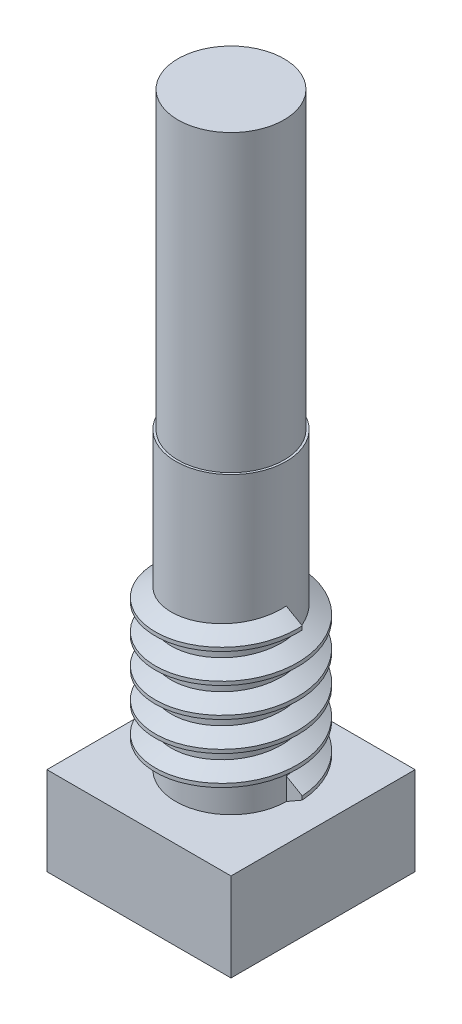
SolidWorks part; units mm, degrees
ref_plane "Front Plane" through (0, 0, 0) normal (0, 0, 1) x (1, 0, 0)
ref_plane "Top Plane" through (0, 0, 0) normal (0, 1, 0) x (1, 0, 0)
ref_plane "Right Plane" through (0, 0, 0) normal (1, 0, 0) x (0, 0, -1)
sketch "Sketch2" plane through (0, 0, 0) normal (0, 1, 0) x (1, 0, 0)
  line L1 (3.9688, -3.9688) -> (-3.9687, -3.9688)
  line L2 (3.9688, -3.9688) -> (3.9688, 3.9687)
  line L3 (3.9688, 3.9687) -> (-3.9687, 3.9687)
  line L4 (-3.9687, -3.9688) -> (-3.9687, 3.9687)
  line L5 (3.9688, -3.9688) -> (-3.9687, 3.9687) construction
  line L6 (3.9688, 3.9687) -> (-3.9687, -3.9688) construction
  dimension "D2" = 7.9375
  dimension "D3" = 7.9375
extrude "Boss-Extrude1" add sketch "Sketch2" along normal blind 3.81
sketch "Sketch3" plane through (0, 3.81, 0) normal (0, 1, 0) x (1, 0, 0)
  circle A0 centre (0, 0) radius 2.3825
  dimension "D1" = 4.765
extrude "Boss-Extrude2" add sketch "Sketch3" along normal blind 25.4
thread "Thread2" pitch 1.27 method extrude profile "Thread Profile2" start angle 0, offset 0, length 6.35, pitch 1.27, diameter 4.765
ref_plane "Plane2" through (2.3825, 3.81, 0) normal (0, 0, 1) x (1, 0, 0)
sketch "Thread Profile2" plane through (2.3825, 3.81, 0) normal (0, 0, 1) x (1, 0, 0)
  line L0 (0, 0) -> (0, 1.27) construction
  line L1 (0, 0) -> (0.6874, 0.3969)
  line L2 (0.6874, 0.3969) -> (0.6874, 0.5556)
  line L3 (0.6874, 0.5556) -> (0, 0.9525)
  line L4 (0.6874, 0.4762) -> (0, 0.4762) construction
  line L11 (0, 0) -> (0, 0.9525)
  point P2 (0, 0)
  dimension "Pitch" = 1.27
  dimension "Profile_Angle" = 60
  dimension "Profile_Land" = 0.1588
  dimension "Profile_Height" = 0.6874
sketch "Sketch4" plane through (0, 29.21, 0) normal (0, 1, 0) x (1, 0, 0)
  circle A0 centre (0, 0) radius 2.286
  dimension "D1" = 4.572
extrude "Cut-Extrude1" cut sketch "Sketch4" against normal blind 12.7 flip side to cut
